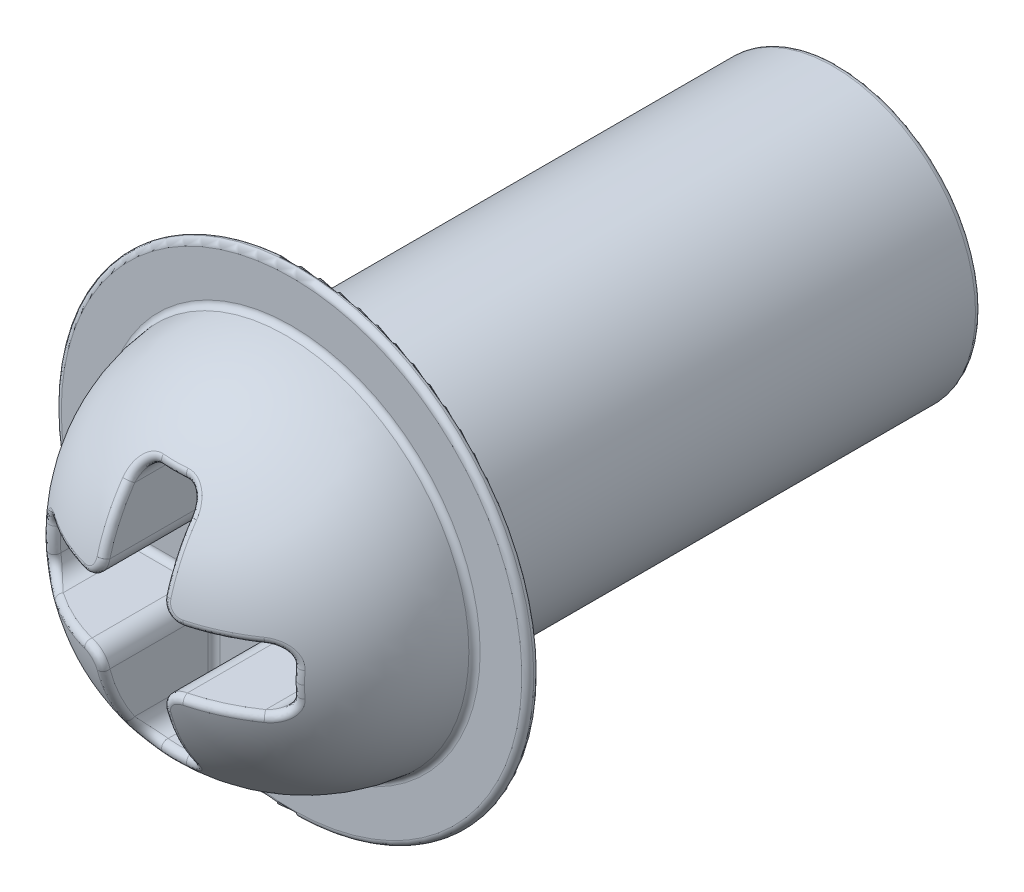
SolidWorks part; units mm, degrees
material "moto_grey"
ref_plane "Front Plane" through (0, 0, 0) normal (0, 0, 1) x (1, 0, 0)
ref_plane "Top Plane" through (0, 0, 0) normal (0, 1, 0) x (1, 0, 0)
ref_plane "Right Plane" through (0, 0, 0) normal (1, 0, 0) x (0, 0, -1)
sketch "Sketch1" plane through (0, 0, 0) normal (0, 0, 1) x (1, 0, 0)
  circle A0 centre (0, 0) radius 2.385
  dimension "D1" = 4.77
extrude "Boss-Extrude1" add sketch "Sketch1" along normal blind 9
sketch "Sketch2" plane through (0, 0, 9) normal (0, 0, 1) x (1, 0, 0)
  circle A0 centre (0, 0) radius 3.0815
extrude "Boss-Extrude2" add sketch "Sketch2" along normal blind 3
sketch "Sketch3" plane through (0, 0, 12) normal (0, 0, 1) x (1, 0, 0)
  line L1 (-0.5, -2) -> (0.5, -2)
  line L2 (-0.5, -2) -> (-0.5, 2)
  line L3 (-0.5, 2) -> (0.5, 2)
  line L4 (0.5, -2) -> (0.5, 2)
  line L5 (-0.5, -2) -> (0.5, 2) construction
  line L6 (-0.5, 2) -> (0.5, -2) construction
  line L7 (-2, -0.5) -> (2, -0.5)
  line L8 (-2, -0.5) -> (-2, 0.5)
  line L9 (-2, 0.5) -> (2, 0.5)
  line L10 (2, -0.5) -> (2, 0.5)
  line L11 (-2, -0.5) -> (2, 0.5) construction
  line L12 (-2, 0.5) -> (2, -0.5) construction
  point P0 (0, 0)
  point P6 (0, 0)
  dimension "D1" = 4
  dimension "D2" = 1
  dimension "D3" = 1
  dimension "D4" = 4
extrude "Cut-Extrude1" cut sketch "Sketch3" against normal blind 2 contours L2 L9 L4 L3 | L9 L2 L7 L4 | L7 L2 L1 L4 | L7 L10 L9 L4 | L9 L8 L7 L2 region at (0, -1.25, 12) region at (-1.25, 0, 12) region at (0, 0, 12) region at (1.25, 0, 12) region at (0, 1.25, 12)
fillet "Fillet1" radius 3 1 edges at (3.0815, 0, 12)
fillet "Fillet4" radius 0.3 12 edges at (0.5, -2, 10.6269) (-0.5, -2, 10.6269) (2, -0.5, 10.6269) (2, 0.5, 10.6269) (-2, 0.5, 10.6269) (-2, -0.5, 10.6269) (-0.5, -0.5, 10.967) (0.5, -0.5, 10.967) (0.5, 0.5, 10.967) (-0.5, 0.5, 10.967) (0.5, 2, 10.6269) (-0.5, 2, 10.6269)
fillet "Fillet5" radius 0.1 24 edges at (-0.4121, -1.9121, 10) (-0.5, -1.25, 10) (-0.5879, -0.5879, 10) (-1.25, -0.5, 10) (-1.9121, -0.4121, 10) (-2, 0, 10) (-1.9121, 0.4121, 10) (-1.25, 0.5, 10) (-0.5879, 0.5879, 10) (-0.5, 1.25, 10) (-0.4121, 1.9121, 10) (0, 2, 10) (0.4121, 1.9121, 10) (0.5, 1.25, 10) (0.5879, 0.5879, 10) (1.25, 0.5, 10) (1.9121, 0.4121, 10) (2, 0, 10) (1.9121, -0.4121, 10) (1.25, -0.5, 10) (0.5879, -0.5879, 10) (0.5, -1.25, 10) (0.4121, -1.9121, 10) (0, -2, 10)
fillet "Fillet7" radius 0.1 1 edges at (2.385, 0, 9)
fillet "Fillet8" radius 0.1 1 edges at (2.385, 0, 0)
sketch "Sketch4" plane through (0, 0, 9) normal (0, 0, -1) x (-1, 0, 0)
  circle A0 centre (0, 0) radius 2.8423
  circle A1 centre (0, 0) radius 3.9668
  circle A2 centre (0, 0) radius 3.0815
  circle A3 centre (0, 0) radius 3.0815
  circle M3 centre (0, 0) radius 3.0815
  dimension "D1" = 0
extrude "Boss-Extrude4" add sketch "Sketch4" against normal blind 0.2 contours A0 M3 | A1 M3 region at (3.8546, 0, 9) region at (2.9943, 0, 9)
fillet "Fillet9" radius 0.1 1 edges at (-3.0748, 0, 9.2)
fillet "Fillet10" radius 0.1 25 edges at (-0.4222, -1.9015, 11.3488) (0.4132, -1.9111, 11.3429) (0.5, -1.1436, 11.7639) (0.6164, -0.5627, 11.9039) (1.1943, -0.5, 11.7437) (1.9015, -0.4222, 11.3488) (1.9111, 0.4132, 11.3429) (1.1436, 0.5, 11.7639) (0.5627, 0.6164, 11.9039) (0.5, 1.1943, 11.7437) (0.4222, 1.9015, 11.3488) (-0.4132, 1.9111, 11.3429) (-0.5, 1.1436, 11.7639) (-0.6164, 0.5627, 11.9039) (-1.1943, 0.5, 11.7437) (-1.9015, 0.4222, 11.3488) (-1.9111, -0.4132, 11.3429) (-1.1436, -0.5, 11.7639) (-0.5627, -0.6164, 11.9039) (-0.5, -1.1943, 11.7437)
fillet "Fillet11" radius 0.1 2 edges at (-3.9668, 0, 9) (-3.9668, 0, 9.2)
